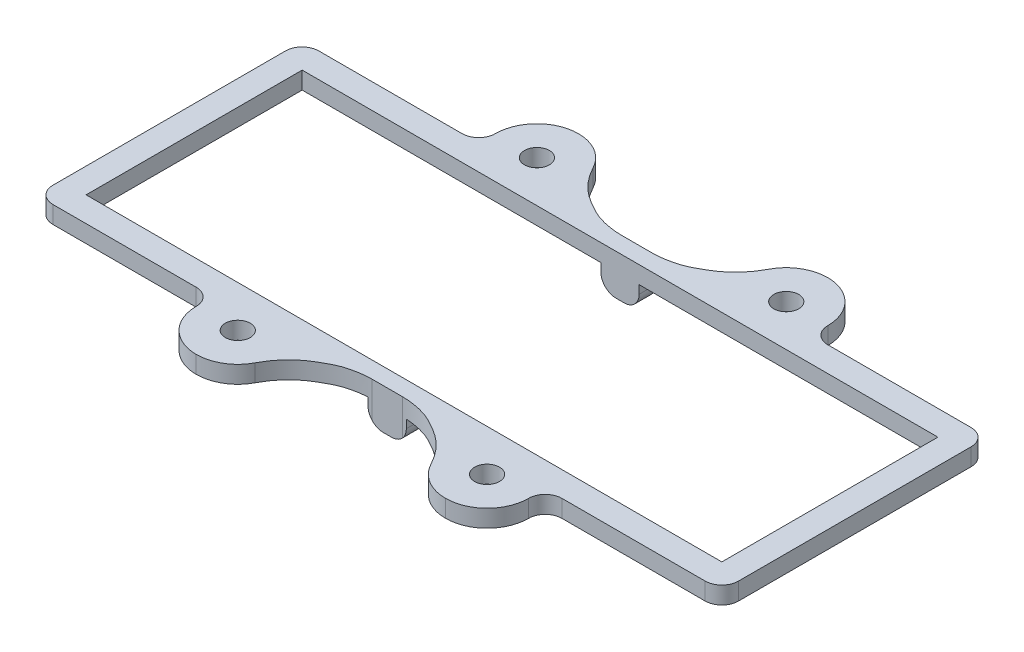
SolidWorks part; units mm, degrees
ref_plane "Front Plane" through (0, 0, 0) normal (0, 0, 1) x (1, 0, 0)
ref_plane "Top Plane" through (0, 0, 0) normal (0, 1, 0) x (1, 0, 0)
ref_plane "Right Plane" through (0, 0, 0) normal (1, 0, 0) x (0, 0, -1)
sketch "Sketch1" plane through (0, 0, 0) normal (0, 1, 0) x (1, 0, 0)
  line L0 (-44.593, 3.4751) -> (37.907, 3.4751) construction
  line L1 (-44.593, 19.4751) -> (37.907, 19.4751)
  line L2 (-44.593, 19.4751) -> (-44.593, -12.5249)
  line L3 (-44.593, -12.5249) -> (37.907, -12.5249)
  line L4 (37.907, 19.4751) -> (37.907, -12.5249)
  line L5 (-41.593, 16.4751) -> (34.907, 16.4751)
  line L6 (-41.593, 16.4751) -> (-41.593, -9.5249)
  line L7 (-41.593, -9.5249) -> (34.907, -9.5249)
  line L8 (34.907, 16.4751) -> (34.907, -9.5249)
  line L9 (-3.343, 19.4751) -> (-3.343, -12.5249) construction
  line L10 (16.657, -12.5249) -> (16.657, -19.5249)
  line L11 (-23.343, 19.4751) -> (16.657, 19.4751)
  line L12 (-23.343, 19.4751) -> (-23.343, 26.4751)
  line L13 (-23.343, 26.4751) -> (16.657, 26.4751)
  line L14 (16.657, 19.4751) -> (16.657, 26.4751)
  line L15 (-23.343, -19.5249) -> (16.657, -19.5249)
  line L16 (-23.343, -12.5249) -> (-23.343, -19.5249)
  line L17 (-23.343, -12.5249) -> (16.657, -12.5249)
  line L18 (-25.2775, 21.4751) -> (22.0201, 21.4751) construction
  circle A0 centre (-18.343, 21.4751) radius 1.5
  circle A1 centre (11.657, 21.4751) radius 1.5
  circle A2 centre (11.657, -14.5249) radius 1.5
  circle A3 centre (-18.343, -14.5249) radius 1.5
  dimension "D1" = 82.5
  dimension "D2" = 32
  dimension "D3" = 76.5
  dimension "D4" = 26
  dimension "D5" = 13
  dimension "D6" = 38.25
  dimension "D7" = 40
  dimension "D8" = 20
  dimension "D9" = 7
  dimension "D10" = 30
  dimension "D12" = 15
  dimension "D13" = 2
extrude "Boss-Extrude1" add sketch "Sketch1" along normal blind 2.085 contours L3 L16 L15 L10 A2 A3 | L4 L1 L2 L3 L5 L8 L7 L6 | L1 L14 L13 L12 A1 A0 region at (-33.968, 0, -18.5902) region at (-3.343, 0, -23.0548) region at (-3.343, 0, 16.1047)
sketch "Sketch2" plane through (0, 0, 0) normal (0, -1, 0) x (1, 0, 0)
  line L0 (-3.343, 19.5249) -> (-3.343, -26.4751) construction
  line L1 (-23.343, 19.5249) -> (16.657, 19.5249) construction
  line L2 (-23.343, -26.4751) -> (16.657, -26.4751) construction
  line L3 (-41.593, -3.4751) -> (34.907, -3.4751) construction
  line L4 (-5.843, 19.5249) -> (-0.843, 19.5249)
  line L5 (-5.843, 19.5249) -> (-5.843, 9.5249)
  line L6 (-5.843, 9.5249) -> (-0.843, 9.5249)
  line L7 (-0.843, 19.5249) -> (-0.843, 9.5249)
  line L8 (-41.593, -16.4751) -> (-41.593, 9.5249) construction
  line L9 (34.907, -16.4751) -> (34.907, 9.5249) construction
  line L10 (-0.843, -26.4751) -> (-0.843, -16.4751)
  line L11 (-5.843, -16.4751) -> (-0.843, -16.4751)
  line L12 (-5.843, -26.4751) -> (-5.843, -16.4751)
  line L13 (-5.843, -26.4751) -> (-0.843, -26.4751)
  dimension "D1" = 5
  dimension "D2" = 10
  dimension "D3" = 2.5
extrude "Boss-Extrude2" add sketch "Sketch2" along normal blind 3
fillet "Fillet1" radius 2 4 edges at (-5.843, -3, 14.5249) (-0.843, -3, 14.5249) (-0.843, -3, -21.4751) (-5.843, -3, -21.4751)
fillet "Fillet2" radius 2 4 edges at (-44.593, 1.0425, 12.5249) (-44.593, 1.0425, -19.4751) (37.907, 1.0425, 12.5249) (37.907, 1.0425, -19.4751)
sketch "Sketch3" plane through (0, 0, -26.4751) normal (0, 0, -1) x (-1, 0, 0)
  line L8 (23.343, 0) -> (5.843, 0) construction
  line L9 (6.1655, 0) -> (0.1244, 0)
  line L10 (6.1655, 0) -> (6.1655, -3.3793)
  line L11 (6.1655, -3.3793) -> (0.1244, -3.3793)
  line L12 (0.1244, 0) -> (0.1244, -3.3793)
  line L16 (2.843, -2.8) -> (3.843, -2.8)
  line L17 (5.643, 0.2) -> (23.143, 0.2)
  line L18 (23.143, 0.2) -> (23.143, 1.885)
  line L19 (23.143, 1.885) -> (-16.457, 1.885)
  line L20 (-16.457, 1.885) -> (-16.457, 0.2)
  line L21 (-16.457, 0.2) -> (1.043, 0.2)
  line L22 (2.843, -2.8) -> (3.843, -2.8)
  line L23 (5.643, 0.2) -> (23.143, 0.2)
  line L24 (23.143, 0.2) -> (23.143, 1.885)
  line L25 (23.143, 1.885) -> (-16.457, 1.885)
  line L26 (-16.457, 1.885) -> (-16.457, 0.2)
  line L27 (-16.457, 0.2) -> (1.043, 0.2)
  line L28 (1.043, 0.2) -> (1.043, -1)
  line L29 (1.043, 0.2) -> (1.043, -1)
  line L30 (5.643, -1) -> (5.643, 0.2)
  line L31 (5.643, -1) -> (5.643, 0.2)
  arc A4 (1.043, -1) -> (2.843, -2.8) centre (2.843, -1) ccw
  arc A5 (3.843, -2.8) -> (5.643, -1) centre (3.843, -1) ccw
  arc A6 (1.043, -1) -> (2.843, -2.8) centre (2.843, -1) ccw
  arc A7 (3.843, -2.8) -> (5.643, -1) centre (3.843, -1) ccw
  line M11 (0.843, 0) -> (0.843, -1)
  arc M12 (0.843, -1) -> (2.843, -3) centre (2.843, -1) ccw
  line M13 (2.843, -3) -> (3.843, -3)
  arc M14 (3.843, -3) -> (5.843, -1) centre (3.843, -1) ccw
  line M15 (5.843, -1) -> (5.843, 0)
  dimension "D1" = 0.2
extrude "Cut-Extrude1" cut sketch "Sketch3" against normal through all contours A7 L22 A6 L29 L9 L31 M11 M12 M13 M14 M15 region at (-5.7846, -0.5, -26.4751)
sketch "Sketch4" plane through (0, 2.085, 0) normal (0, 1, 0) x (1, 0, 0)
  line L0 (-3.343, 18.4751) -> (7.657, 18.4751)
  line L1 (7.657, 18.4751) -> (-14.343, 18.4751)
  line L2 (-5.0256, 18.4751) -> (-1.6603, 18.4751)
  line L3 (37.907, 3.4751) -> (-44.593, 3.4751) construction
  line L4 (37.907, 17.4751) -> (37.907, -10.5249) construction
  line L5 (-44.593, 17.4751) -> (-44.593, -10.5249) construction
  line L6 (11.657, 26.4751) -> (11.657, 33.2921)
  line L7 (11.657, 33.2921) -> (-18.343, 33.2921)
  line L8 (-18.343, 33.2921) -> (-18.343, 26.4751)
  line L9 (-18.343, -26.342) -> (-18.343, -19.5249)
  line L10 (11.657, -26.342) -> (-18.343, -26.342)
  line L11 (11.657, -19.5249) -> (11.657, -26.342)
  line L12 (-5.0256, -11.5249) -> (-1.6603, -11.5249)
  line L13 (7.657, -11.5249) -> (-14.343, -11.5249)
  line L14 (-3.343, -11.5249) -> (7.657, -11.5249)
  circle A0 centre (-18.343, 21.4751) radius 5
  circle A1 centre (11.657, 21.4751) radius 5
  circle A2 centre (11.657, -14.5249) radius 5
  circle A3 centre (-18.343, -14.5249) radius 5
  spline S0 degree 3 poles (-13.9208, 23.8084) (-13.3837, 22.8069) (-12.2321, 21.2227) (-10.1423, 19.8877) (-8.5768, 19.0482) (-6.9016, 18.5983) (-5.7419, 18.469) (-5.0256, 18.4751) knots 0 0 0 0 0.314938 0.52444 0.679222 0.802825 1 1 1 1
  spline S1 degree 3 poles (7.2349, 23.8084) (6.6978, 22.8069) (5.5462, 21.2227) (3.4564, 19.8877) (1.8909, 19.0482) (0.2157, 18.5983) (-0.944, 18.469) (-1.6603, 18.4751) knots 0 0 0 0 0.314938 0.52444 0.679222 0.802825 1 1 1 1
  spline S2 degree 3 poles (7.2349, -16.8583) (6.6978, -15.8568) (5.5462, -14.2726) (3.4564, -12.9376) (1.8909, -12.0981) (0.2157, -11.6482) (-0.944, -11.5188) (-1.6603, -11.5249) knots 0 0 0 0 0.314938 0.52444 0.679222 0.802825 1 1 1 1
  spline S3 degree 3 poles (-13.9208, -16.8583) (-13.3837, -15.8568) (-12.2321, -14.2726) (-10.1423, -12.9376) (-8.5768, -12.0981) (-6.9016, -11.6482) (-5.7419, -11.5188) (-5.0256, -11.5249) knots 0 0 0 0 0.314938 0.52444 0.679222 0.802825 1 1 1 1
  line M7 (-23.343, -19.5249) -> (16.657, -19.5249)
  line M15 (16.657, 26.4751) -> (-23.343, 26.4751)
extrude "Cut-Extrude2" cut sketch "Sketch4" against normal through all contours S1 A1 A0 S0 L1 L0 M15 | L7 L8 L6 M15 | S3 A3 A2 S2 L14 L13 L12 M7 | L11 L9 L10 M7 region at (-3.343, 2.085, -23.0852) region at (-3.343, 2.085, -29.8836) region at (-3.343, 2.085, 22.9335) region at (-3.343, 2.085, 16.1351)
fillet "Fillet3" radius 5 4 edges at (16.657, 1.0425, -26.4751) (-23.343, 1.0425, -26.4751) (-23.343, 1.0425, 19.5249) (16.657, 1.0425, 19.5249)
fillet "Fillet4" radius 2 4 edges at (16.657, 1.0425, 12.5249) (-23.343, 1.0425, 12.5249) (-23.343, 1.0425, -19.4751) (16.657, 1.0425, -19.4751)
